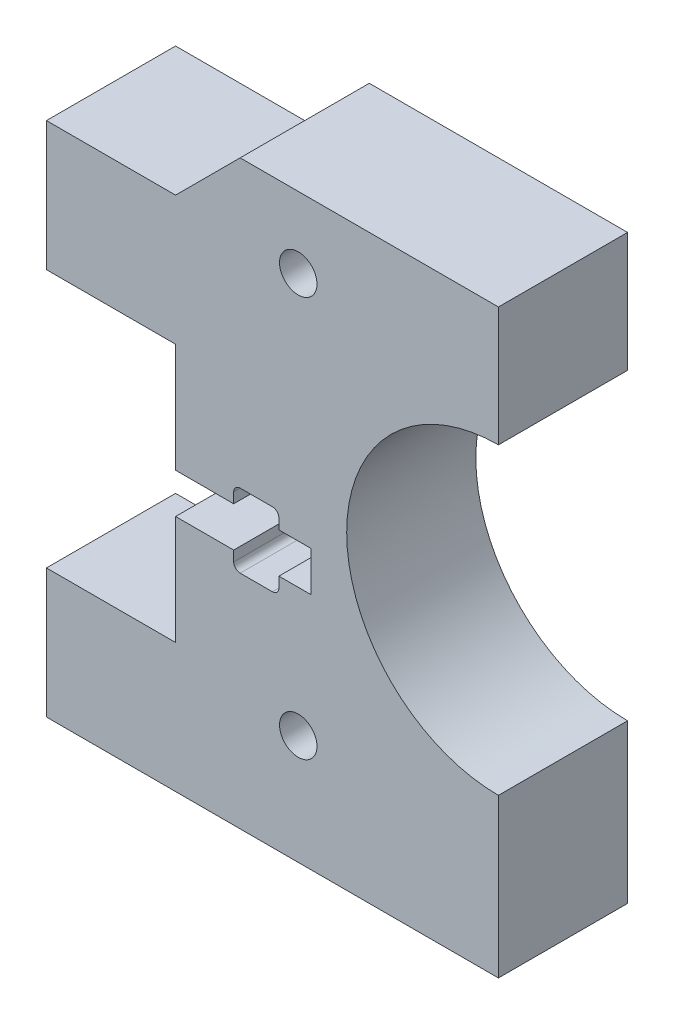
SolidWorks part; units mm, degrees
ref_plane "Front Plane" through (0, 0, 0) normal (0, 0, 1) x (1, 0, 0)
ref_plane "Top Plane" through (0, 0, 0) normal (0, 1, 0) x (1, 0, 0)
ref_plane "Right Plane" through (0, 0, 0) normal (1, 0, 0) x (0, 0, -1)
sketch "Sketch1" plane through (0, 0, 0) normal (0, 0, 1) x (1, 0, 0)
  line L0 (0, 0) -> (0, -50) construction
  line L1 (-10, -40) -> (0, -40) construction
  line L2 (25, -50) -> (25, 0) construction
  line L3 (25, 0) -> (0, 0) construction
  line L4 (0, 0) -> (0, -5)
  line L5 (0, -5) -> (-10, -5)
  line L6 (-10, -5) -> (-10, -15)
  line L7 (-10, -15) -> (0, -15)
  line L8 (0, -15) -> (0, -35)
  line L9 (25, -50) -> (0, -50) construction
  line L10 (0, -50) -> (25, -50)
  line L11 (-10, -35) -> (0, -35)
  line L12 (-10, -45) -> (-10, -35)
  line L13 (0, -45) -> (-10, -45)
  line L14 (25, -50) -> (25, 0)
  line L15 (0, 0) -> (25, 0)
  line L16 (0, -50) -> (0, -45)
  line L17 (-10, -10) -> (0, -10) construction
  line L18 (0, -25) -> (25, -25) construction
  dimension "D1" = 10
  dimension "D6" = 25
  dimension "D2" = 25
extrude "Boss-Extrude1" add sketch "Sketch1" along normal blind 10
sketch "Sketch2" plane through (0, 0, 10) normal (0, 0, 1) x (1, 0, 0)
  line L0 (25, -21) -> (0, -21) construction
  line L1 (25, -50) -> (25, 0) construction
  line L2 (0, -15) -> (0, -35) construction
  line L3 (25, -21) -> (9.5, -5.5) construction
  line L4 (25, -21) -> (9.5, -36.5) construction
  circle A0 centre (25, -21) radius 11.75
  circle A1 centre (9.5, -5.5) radius 1.45
  circle A2 centre (9.5, -36.5) radius 1.45
  point P6 (0, -25)
  dimension "D2" = 23.5
  dimension "D5" = 2.9
  dimension "D1" = 4
  dimension "D3" = 45
  dimension "D4" = 15.5
extrude "motor" cut sketch "Sketch2" against normal through all
sketch "Sketch3" plane through (0, 0, 10) normal (0, 0, 1) x (1, 0, 0)
  line L0 (0, -25) -> (10.5, -25) construction
  line L1 (0, -15) -> (0, -35) construction
  line L2 (10.5, -26.55) -> (10.5, -23.45) construction
  line L3 (10.5, -23.45) -> (0, -23.45) construction
  line L4 (0, -26.55) -> (0, -23.45)
  line L5 (0, -23.45) -> (4.5, -23.45)
  line L6 (4.5, -23.45) -> (4.5, -22.65)
  line L7 (5, -22.15) -> (7.5, -22.15)
  line L8 (8, -22.65) -> (8, -23.45)
  line L9 (8, -23.45) -> (10.5, -23.45)
  line L10 (10.5, -23.45) -> (10.5, -26.55)
  line L11 (10.5, -26.55) -> (0, -26.55) construction
  line L12 (8, -26.55) -> (10.5, -26.55)
  line L13 (8, -27.35) -> (8, -26.55)
  line L14 (5, -27.85) -> (7.5, -27.85)
  line L15 (4.5, -26.55) -> (4.5, -27.35)
  line L16 (0, -26.55) -> (4.5, -26.55)
  arc A0 (5, -27.85) -> (4.5, -27.35) centre (5, -27.35) cw
  arc A1 (8, -27.35) -> (7.5, -27.85) centre (7.5, -27.35) cw
  arc A2 (7.5, -22.15) -> (8, -22.65) centre (7.5, -22.65) cw
  arc A3 (4.5, -22.65) -> (5, -22.15) centre (5, -22.65) cw
  point P18 (4.5, -27.85)
  point P21 (8, -27.85)
  point P24 (8, -22.15)
  point P27 (4.5, -22.15)
  dimension "D6" = 0.5
  dimension "D1" = 1.55
  dimension "D2" = 8
  dimension "D3" = 10.5
  dimension "D4" = 2.85
  dimension "D5" = 3.5
extrude "screw" cut sketch "Sketch3" against normal through all
sketch "Sketch4" plane through (0, 0, 10) normal (0, 0, 1) x (1, 0, 0)
  line L0 (0, -45) -> (25, -45)
  line L1 (25, -50) -> (25, -32.75) construction
  line L2 (25, -45) -> (25, -50)
  line L3 (25, -50) -> (0, -50)
  line L4 (0, -50) -> (0, -45)
  line L5 (0, -5) -> (5, 0)
  line L6 (25, 0) -> (0, 0) construction
  line L7 (5, 0) -> (0, 0)
  line L8 (0, 0) -> (0, -5)
  dimension "D1" = 45
extrude "Cut-Extrude3" cut sketch "Sketch4" against normal through all
equation "\"X-ROD-SPACING\"=45"
equation "\"Y-ROD-SPACING\"=75"
equation "\"Z-ROD-SPACING\"=17.5"
equation "\"Y-BED-OFFSET\"=2"
equation "\"Y-BED-ROD-INSET\"=3.5"
equation "\"T-SLOT-NUT-FILLET-RADIUS\"=0.5"
equation "\"T-SLOT-SCREW-SHAFT-RADIUS\"=1.55"
equation "\"T-SLOT-SCREW-SHAFT-CUTOUT-LENGTH\"=11.0"
equation "\"T-SLOT-NUT-DEPTH\"=3.5"
equation "\"T-SLOT-NUT-WIDTH\"=2.85"
equation "\"T-SLOT-NUT-END-DISTANCE\"=8"
equation "\"ACRYLIC-THICKNESS\"=10"
equation "\"ACRYLIC-THICKNESS2\"=4.5"
equation "\"ACRYLIC-TAB-CUTOUT-SIZE\"=\"ACRYLIC-THICKNESS\"+\"ACRYLIC-TAB-TOLERANCE\"*2"
equation "\"ACRYLIC-TAB-WIDTH\"=\"ACRYLIC-THICKNESS\""
equation "\"ACRYLIC-M3-HOLE\"=2.9"
equation "\"SMOOTHROD-CAP-SCREW-DISTANCE\"=20"
equation "\"FRAME-WIDTH-INNER\"=370"
equation "\"NEMA17-HOLE-SPACING\"=31"
equation "\"NEMA17-CENTRAL-CUTOUT\"=22.5"
equation "\"Z-BRACKET-REACH\"=55"
equation "\"TOP-BRACKET-SPACING\"=40"
equation "\"SMOOTHROD-X-LENGTH\"=350"
equation "\"SMOOTHROD-Y-LENGTH\"=350"
equation "\"SMOOTHROD-Z-LENGTH\"=350"
equation "\"SMOOTHROD-TIGHTENING-HEADROOM\"=.25"
equation "\"LEADSCREW-Z-LENGTH\"=300"
equation "\"SCREW-LENGTH-FRAME\"=\"ACRYLIC-THICKNESS\" + 10"
equation "\"SCREW-HEAD-RADIUS\"=6"
equation "\"PRINTED-X-SMOOTHROD-DIAMETER\"=8.4"
equation "\"PRINTED-X-SMOOTHROD-CUTOUT\"=10"
equation "\"PRINTED-X-BASE-HEIGHT\"=10"
equation "\"PRINTED-LM8UU-CUTOUT-SIZE\"=15.5"
equation "\"PRINTED-LM8UU-CUTOUT-LENGTH\"=24.5"
equation "\"PRINTED-X-IDLER-HEIGHT\"=16"
equation "\"PSU-MOUNTING-WIDTH\"=95"
equation "\"PSU-MOUNTING-HEIGHT\"=177"
equation "\"D1@Sketch1\"=10"
equation "\"D3@Sketch1\"=10"
equation "\"D1@Boss-Extrude1\"=\"ACRYLIC-THICKNESS\""
equation "\"D2@Sketch2\"=\"NEMA17-CENTRAL-CUTOUT\"+1"
equation "\"D4@Sketch2\"=\"NEMA17-HOLE-SPACING\"/2"
equation "\"D5@Sketch2\"=\"ACRYLIC-M3-HOLE\""
equation "\"D1@Sketch3\"=\"T-SLOT-SCREW-SHAFT-RADIUS\""
equation "\"D4@Sketch3\"=\"T-SLOT-NUT-WIDTH\""
equation "\"D2@Sketch3\"=\"T-SLOT-NUT-END-DISTANCE\""
equation "\"D5@Sketch3\"=\"T-SLOT-NUT-DEPTH\""
equation "\"D6@Sketch3\"=\"T-SLOT-NUT-FILLET-RADIUS\""
